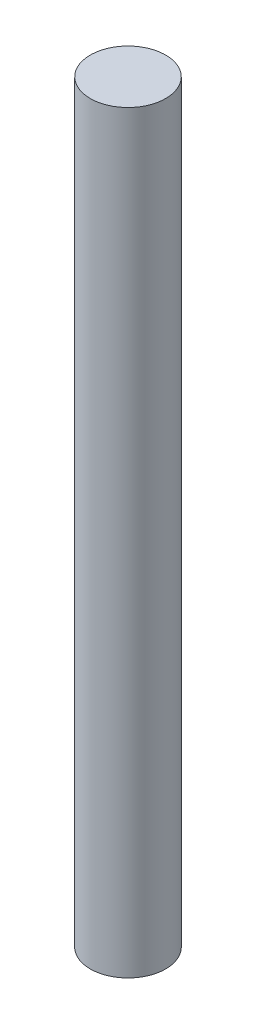
SolidWorks part; units mm, degrees
ref_plane "Front Plane" through (0, 0, 0) normal (0, 0, 1) x (1, 0, 0)
ref_plane "Top Plane" through (0, 0, 0) normal (0, 1, 0) x (1, 0, 0)
ref_plane "Right Plane" through (0, 0, 0) normal (1, 0, 0) x (0, 0, -1)
sketch "Sketch2" plane through (0, 0, 0) normal (0, 1, 0) x (1, 0, 0)
  circle A0 centre (0, 0) radius 1
  dimension "D1" = 2
extrude "Boss-Extrude1" add sketch "Sketch2" along normal blind 10 and the other way blind 10
